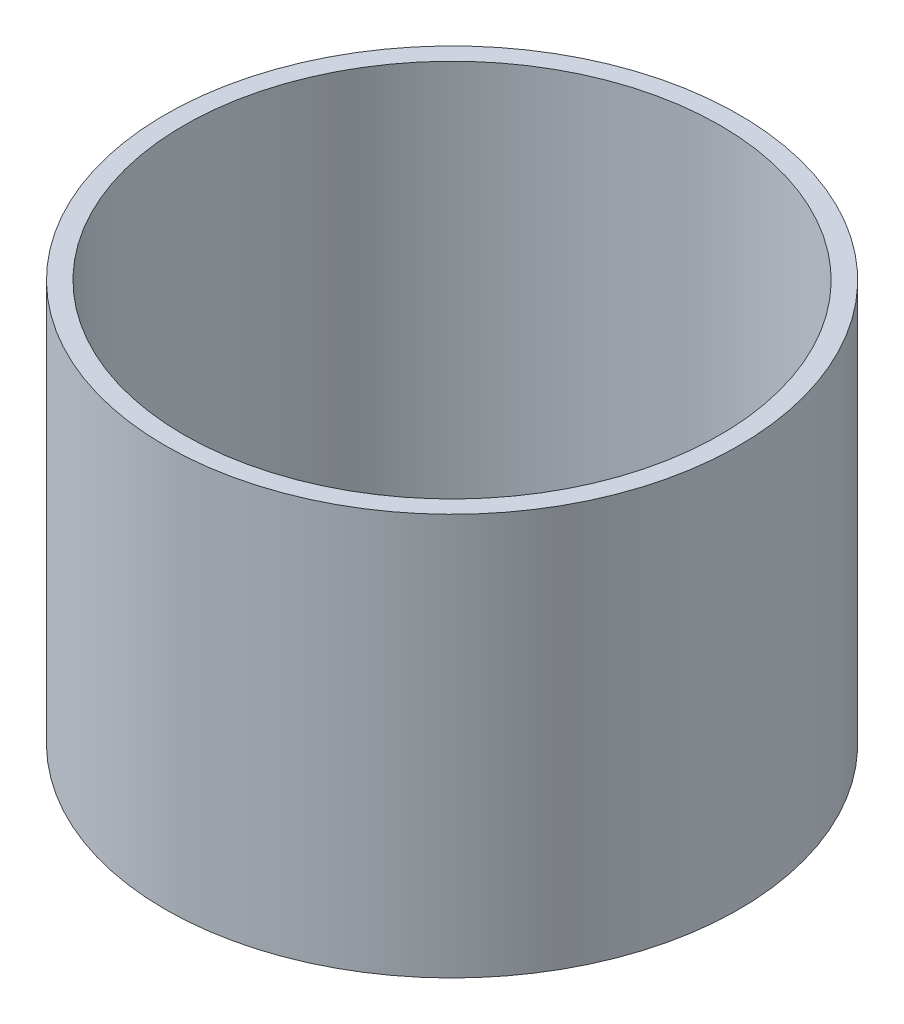
SolidWorks part; units mm, degrees
material "S1D_75 Degrees Custom Wound Fiberglass"
ref_plane "Front Plane" through (0, 0, 0) normal (0, 0, 1) x (1, 0, 0)
ref_plane "Top Plane" through (0, 0, 0) normal (0, 1, 0) x (1, 0, 0)
ref_plane "Right Plane" through (0, 0, 0) normal (1, 0, 0) x (0, 0, -1)
ref_axis "Axis1" through (0, -55, 0) along (0, 1, 0)
sketch "Sketch1" plane through (0, 0, 0) normal (0, 1, 0) x (1, 0, 0)
  circle A0 centre (0, 0) radius 38.1508
  circle A1 centre (0, 0) radius 40.8178
  dimension "D1" = 76.3016
  dimension "D2" = 2.667
extrude "Boss-Extrude1" add sketch "Sketch1" along normal blind 57.15
ref_plane "Plane1" through (0, 57.15, 0) normal (0, 1, 0) x (1, 0, 0)
ref_plane "Switch Band Midplane" through (0, 28.575, 0) normal (0, 1, 0) x (1, 0, 0)
